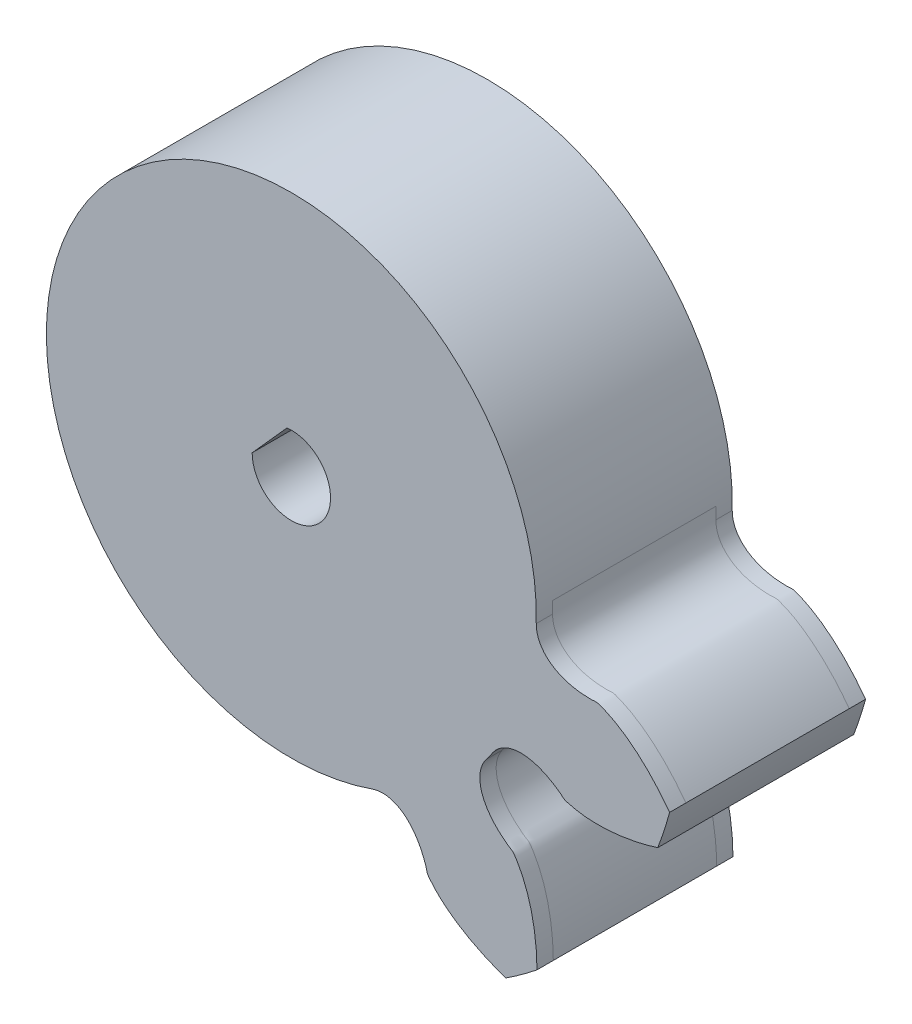
SolidWorks part; units mm, degrees
note: '?' marks a value the reader was unsure of.
ref_plane "Front Plane" through (0, 0, 0) normal (0, 0, 1) x (1, 0, 0)
ref_plane "Top Plane" through (0, 0, 0) normal (0, 1, 0) x (1, 0, 0)
ref_plane "Right Plane" through (0, 0, 0) normal (1, 0, 0) x (0, 0, -1)
ref_axis "Axis1" through (0, 0, 55) along (0, 0, -1)?
sketch "SketchRevolveSpur01" plane through (0, 0, 0) normal (1, 0, 0) x (0, 0, -1)
  line L0 (0, 0) -> (1, 0) construction
  line L1 (-3, 0) -> (-3, 12)
  line L2 (-3, 12) -> (3, 12)
  line L3 (3, 12) -> (3, 0)
  line L4 (3, 0) -> (-3, 0)
  dimension "Side1" = 3
  dimension "OutsideRadius" = 12
  dimension "Side2" = 3
revolve "Spur01" add sketch "SketchRevolveSpur01" angle 360 about L0
sketch "SketchToothSpur01" plane through (0, 0, 0) normal (0, 0, 1) x (1, 0, 0)
  arc A0 (11.6557, 3.249) -> (11.6557, -3.249) centre (0, 0) cw
  spline S0 degree 3 poles (11.6557, -3.249) (11.5423, -3.0893) (11.3677, -2.8624) (11.1235, -2.583) (10.948, -2.3979) (10.7762, -2.2308) (10.6093, -2.0811) (10.4483, -1.9481) (10.2945, -1.8312) (10.1487, -1.7294) (10.0119, -1.6419) (9.8851, -1.5678) (9.769, -1.5061) (9.6644, -1.4561) (9.5722, -1.4158) (9.4742, -1.38) (9.3515, -1.3286) (9.2141, -1.3558) (9.0897, -1.351) (8.9912, -1.3478) (8.8951, -1.3404) (8.8013, -1.3301) (8.7098, -1.3167) (8.6206, -1.3002) (8.5337, -1.2806) (8.4492, -1.2579) (8.3671, -1.232) (8.2873, -1.2028) (8.2098, -1.1702) (8.1347, -1.1342) (8.0621, -1.0944) (7.9919, -1.0508) (7.9244, -1.0029) (7.8597, -0.9507) (7.7981, -0.8936) (7.74, -0.8313) (7.686, -0.7636) (7.6368, -0.6902) (7.5934, -0.6111) (7.5566, -0.5264) (7.5278, -0.4366) (7.5078, -0.3426) (7.4995, -0.2566) (7.4964, -0.1421) (7.5027, 0) (7.4964, 0.1421) (7.4995, 0.2566) (7.5078, 0.3426) (7.5278, 0.4366) (7.5566, 0.5264) (7.5934, 0.6111) (7.6368, 0.6902) (7.686, 0.7636) (7.74, 0.8313) (7.7981, 0.8936) (7.8597, 0.9507) (7.9244, 1.0029) (7.9919, 1.0508) (8.0621, 1.0944) (8.1347, 1.1342) (8.2098, 1.1702) (8.2873, 1.2028) (8.3671, 1.232) (8.4492, 1.2579) (8.5337, 1.2806) (8.6206, 1.3002) (8.7098, 1.3167) (8.8013, 1.3301) (8.8951, 1.3404) (8.9912, 1.3478) (9.0897, 1.351) (9.2141, 1.3558) (9.3515, 1.3286) (9.4742, 1.38) (9.5722, 1.4158) (9.6644, 1.4561) (9.769, 1.5061) (9.8851, 1.5678) (10.0119, 1.6419) (10.1487, 1.7294) (10.2945, 1.8312) (10.4483, 1.9481) (10.6093, 2.0811) (10.7762, 2.2308) (10.948, 2.3979) (11.1235, 2.583) (11.3677, 2.8624) (11.5423, 3.0893) (11.6557, 3.249) knots 0 0 0 0 0.05171 0.075523 0.097976 0.119068 0.138799 0.15717 0.17418 0.189829 0.204117 0.217044 0.228611 0.238817 0.247662 0.255146 0.266488 0.281932 0.290791 0.299458 0.307939 0.316243 0.324379 0.332357 0.340187 0.347883 0.35546 0.362932 0.370318 0.37764 0.384918 0.392178 0.399448 0.406756 0.414133 0.42161 0.429217 0.436977 0.444912 0.453029 0.461324 0.469778 0.478358 0.484106 0.5 0.515894 0.521642 0.530222 0.538676 0.546971 0.555088 0.563023 0.570783 0.57839 0.585867 0.593244 0.600552 0.607822 0.615082 0.62236 0.629682 0.637068 0.64454 0.652117 0.659813 0.667643 0.675621 0.683757 0.692061 0.700542 0.709209 0.718068 0.733512 0.744854 0.752338 0.761183 0.771389 0.782956 0.795883 0.810171 0.82582 0.84283 0.861201 0.880932 0.902024 0.924477 0.94829 1 1 1 1
extrude "ToothExtrudeCutSpur01" cut sketch "SketchToothSpur01" against normal blind 2.5 and the other way blind 2.5
pattern_circular "PatternSpur01" count 3 every 36 about axis through (0, 0, 55) along (0, 0, -1) of "ToothExtrudeCutSpur01"
sketch "Sketch5" plane through (0, 0, 3) normal (0, 0, 1) x (1, 0, 0)
  circle A0 centre (0, 0) radius 7.5
  circle A1 centre (0, 0) radius 12
  spline S0 degree 3 poles (330.6086, 1970.8831) (-63.5307, -131.6267) (27.9115, -21.7923) (11.1235, -2.583) (10.948, -2.3979) (10.7762, -2.2308) (10.6093, -2.0811) (10.4483, -1.9481) (10.2945, -1.8312) (10.1487, -1.7294) (10.0119, -1.6419) (9.8851, -1.5678) (9.769, -1.5061) (9.6644, -1.4561) (9.5722, -1.4158) (9.4742, -1.38) (9.3515, -1.3286) (9.2141, -1.3558) (9.0897, -1.351) (8.9912, -1.3478) (8.8951, -1.3404) (8.8013, -1.3301) (8.7098, -1.3167) (8.6206, -1.3002) (8.5337, -1.2806) (8.4492, -1.2579) (8.3671, -1.232) (8.2873, -1.2028) (8.2098, -1.1702) (8.1347, -1.1342) (8.0621, -1.0944) (7.9919, -1.0508) (7.9244, -1.0029) (7.8597, -0.9507) (7.7981, -0.8936) (7.74, -0.8313) (7.686, -0.7636) (7.6368, -0.6902) (7.5934, -0.6111) (7.5566, -0.5264) (7.5278, -0.4366) (7.5078, -0.3426) (7.4995, -0.2566) (7.4964, -0.1421) (7.5027, 0) (7.4964, 0.1421) (7.4995, 0.2566) (7.5078, 0.3426) (7.5278, 0.4366) (7.5566, 0.5264) (7.5934, 0.6111) (7.6368, 0.6902) (7.686, 0.7636) (7.74, 0.8313) (7.7981, 0.8936) (7.8597, 0.9507) (7.9244, 1.0029) (7.9919, 1.0508) (8.0621, 1.0944) (8.1347, 1.1342) (8.2098, 1.1702) (8.2873, 1.2028) (8.3671, 1.232) (8.4492, 1.2579) (8.5337, 1.2806) (8.6206, 1.3002) (8.7098, 1.3167) (8.8013, 1.3301) (8.8951, 1.3404) (8.9912, 1.3478) (9.0897, 1.351) (9.2141, 1.3558) (9.3515, 1.3286) (9.4742, 1.38) (9.5722, 1.4158) (9.6644, 1.4561) (9.769, 1.5061) (9.8851, 1.5678) (10.0119, 1.6419) (10.1487, 1.7294) (10.2945, 1.8312) (10.4483, 1.9481) (10.6093, 2.0811) (10.7762, 2.2308) (10.948, 2.3979) (11.1235, 2.583) (27.9114, 21.7922) (-63.5294, 131.6251) (330.5997, -1970.8358) knots -6.637455 -6.637455 -6.637455 -6.637455 0.05171 0.075523 0.097976 0.119068 0.138799 0.15717 0.17418 0.189829 0.204117 0.217044 0.228611 0.238817 0.247662 0.255146 0.266488 0.281932 0.290791 0.299458 0.307939 0.316243 0.324379 0.332357 0.340187 0.347883 0.35546 0.362932 0.370318 0.37764 0.384918 0.392178 0.399448 0.406756 0.414133 0.42161 0.429217 0.436977 0.444912 0.453029 0.461324 0.469778 0.478358 0.484106 0.5 0.515894 0.521642 0.530222 0.538676 0.546971 0.555088 0.563023 0.570783 0.57839 0.585867 0.593244 0.600552 0.607822 0.615082 0.62236 0.629682 0.637068 0.64454 0.652117 0.659813 0.667643 0.675621 0.683757 0.692061 0.700542 0.709209 0.718068 0.733512 0.744854 0.752338 0.761183 0.771389 0.782956 0.795883 0.810171 0.82582 0.84283 0.861201 0.880932 0.902024 0.924477 0.94829 7.637405 7.637405 7.637405 7.637405 only from (11.5805, -3.145) to (11.5805, 3.145) construction
  spline S1 degree 3 poles (1425.924, 1400.1511) (-128.7657, -69.1458) (9.7717, -34.0363) (7.4809, -8.6279) (7.4477, -8.375) (7.4069, -8.1388) (7.3598, -7.9196) (7.3078, -7.7175) (7.2521, -7.5324) (7.194, -7.3643) (7.1347, -7.2132) (7.0756, -7.0787) (7.018, -6.9605) (6.9628, -6.8586) (6.9119, -6.7718) (6.8537, -6.6852) (6.7845, -6.5716) (6.6575, -6.5128) (6.5596, -6.4358) (6.4818, -6.3753) (6.4084, -6.3128) (6.3385, -6.2494) (6.2724, -6.1847) (6.2099, -6.119) (6.1512, -6.052) (6.0962, -5.984) (6.045, -5.9147) (5.9976, -5.8442) (5.954, -5.7723) (5.9145, -5.699) (5.8791, -5.6242) (5.848, -5.5476) (5.8214, -5.4692) (5.7998, -5.3889) (5.7836, -5.3065) (5.7732, -5.222) (5.7693, -5.1355) (5.7726, -5.0472) (5.784, -4.9577) (5.804, -4.8675) (5.8335, -4.7779) (5.8726, -4.6901) (5.9164, -4.6157) (5.9811, -4.5212) (6.0698, -4.41) (6.1482, -4.2913) (6.218, -4.2005) (6.2753, -4.1359) (6.3468, -4.0715) (6.4228, -4.0158) (6.5024, -3.9689) (6.584, -3.9304) (6.667, -3.9) (6.7504, -3.8769) (6.834, -3.8607) (6.9174, -3.8507) (7.0005, -3.8464) (7.0832, -3.8474) (7.1656, -3.8534) (7.2478, -3.8639) (7.3297, -3.8789) (7.4115, -3.8981) (7.4932, -3.9214) (7.5749, -3.9487) (7.6567, -3.98) (7.7384, -4.0151) (7.8203, -4.0542) (7.9022, -4.0971) (7.9841, -4.144) (8.0662, -4.1945) (8.1478, -4.2498) (8.2513, -4.319) (8.3465, -4.4218) (8.4759, -4.4524) (8.5762, -4.481) (8.6746, -4.5026) (8.7886, -4.5236) (8.9187, -4.5419) (9.0649, -4.5565) (9.2269, -4.5662) (9.4047, -4.5695) (9.598, -4.5653) (9.8063, -4.5523) (10.0293, -4.5294) (10.2665, -4.4952) (10.5174, -4.4486) (35.3899, 1.2244) (25.971, 143.8286) (-890.9674, -1788.7613) knots -6.637455 -6.637455 -6.637455 -6.637455 0.05171 0.075523 0.097976 0.119068 0.138799 0.15717 0.17418 0.189829 0.204117 0.217044 0.228611 0.238817 0.247662 0.255146 0.266488 0.281932 0.290791 0.299458 0.307939 0.316243 0.324379 0.332357 0.340187 0.347883 0.35546 0.362932 0.370318 0.37764 0.384918 0.392178 0.399448 0.406756 0.414133 0.42161 0.429217 0.436977 0.444912 0.453029 0.461324 0.469778 0.478358 0.484106 0.5 0.515894 0.521642 0.530222 0.538676 0.546971 0.555088 0.563023 0.570783 0.57839 0.585867 0.593244 0.600552 0.607822 0.615082 0.62236 0.629682 0.637068 0.64454 0.652117 0.659813 0.667643 0.675621 0.683757 0.692061 0.700542 0.709209 0.718068 0.733512 0.744854 0.752338 0.761183 0.771389 0.782956 0.795883 0.810171 0.82582 0.84283 0.861201 0.880932 0.902024 0.924477 0.94829 7.637405 7.637405 7.637405 7.637405 only from (7.5202, -9.3513) to (11.2175, -4.2625) construction
  spline S2 degree 3 poles (1976.5849, 294.6089) (-144.8165, 19.7464) (-12.1006, -33.2796) (0.9808, -11.3773) (1.1026, -11.1531) (1.2084, -10.9381) (1.2992, -10.7331) (1.3759, -10.539) (1.4396, -10.3565) (1.4914, -10.1864) (1.5323, -10.0293) (1.5636, -9.8857) (1.5864, -9.7563) (1.6016, -9.6414) (1.6115, -9.5412) (1.6152, -9.437) (1.6262, -9.3044) (1.5579, -9.1821) (1.524, -9.0623) (1.4966, -8.9676) (1.4739, -8.8739) (1.4547, -8.7815) (1.4392, -8.6904) (1.4273, -8.6004) (1.4191, -8.5118) (1.4146, -8.4244) (1.4139, -8.3383) (1.417, -8.2533) (1.424, -8.1696) (1.4351, -8.0871) (1.4505, -8.0057) (1.4703, -7.9255) (1.4949, -7.8465) (1.5247, -7.7688) (1.5599, -7.6925) (1.6012, -7.6181) (1.6489, -7.5458) (1.7035, -7.4764) (1.7653, -7.4106) (1.8345, -7.3494) (1.911, -7.2943) (1.9942, -7.2462) (2.0735, -7.2117) (2.1813, -7.1734) (2.3185, -7.1355) (2.4517, -7.0855) (2.5615, -7.0532) (2.6459, -7.0345) (2.7414, -7.0245) (2.8357, -7.0241) (2.9277, -7.0329) (3.0164, -7.0498) (3.1013, -7.0739) (3.1824, -7.1043) (3.2596, -7.1403) (3.3329, -7.1812) (3.4026, -7.2266) (3.469, -7.2761) (3.5322, -7.3293) (3.5924, -7.3861) (3.6499, -7.4464) (3.7048, -7.51) (3.7572, -7.5769) (3.8073, -7.647) (3.855, -7.7203) (3.9005, -7.7969) (3.9437, -7.8766) (3.9848, -7.9595) (4.0235, -8.0455) (4.0602, -8.1346) (4.0937, -8.2273) (4.1368, -8.3442) (4.1534, -8.4832) (4.2401, -8.5841) (4.3044, -8.6662) (4.3713, -8.7415) (4.4512, -8.8254) (4.5457, -8.9168) (4.6554, -9.0145) (4.7808, -9.1176) (4.9227, -9.2248) (5.0815, -9.335) (5.2577, -9.4469) (5.4516, -9.5594) (5.6636, -9.6712) (5.894, -9.7809) (29.3507, -19.8111) (105.5512, 101.0944) (-1772.2153, -923.4408) knots -6.637455 -6.637455 -6.637455 -6.637455 0.05171 0.075523 0.097976 0.119068 0.138799 0.15717 0.17418 0.189829 0.204117 0.217044 0.228611 0.238817 0.247662 0.255146 0.266488 0.281932 0.290791 0.299458 0.307939 0.316243 0.324379 0.332357 0.340187 0.347883 0.35546 0.362932 0.370318 0.37764 0.384918 0.392178 0.399448 0.406756 0.414133 0.42161 0.429217 0.436977 0.444912 0.453029 0.461324 0.469778 0.478358 0.484106 0.5 0.515894 0.521642 0.530222 0.538676 0.546971 0.555088 0.563023 0.570783 0.57839 0.585867 0.593244 0.600552 0.607822 0.615082 0.62236 0.629682 0.637068 0.64454 0.652117 0.659813 0.667643 0.675621 0.683757 0.692061 0.700542 0.709209 0.718068 0.733512 0.744854 0.752338 0.761183 0.771389 0.782956 0.795883 0.810171 0.82582 0.84283 0.861201 0.880932 0.902024 0.924477 0.94829 7.637405 7.637405 7.637405 7.637405 only from (0.5875, -11.9856) to (6.5697, -10.0419) construction
  spline S3 degree 3 poles (11.5805, -3.145) (11.4898, -3.0217) (11.3396, -2.8302) (11.1235, -2.583) (10.948, -2.3979) (10.7762, -2.2308) (10.6093, -2.0811) (10.4483, -1.9481) (10.2945, -1.8312) (10.1487, -1.7294) (10.0119, -1.6419) (9.8851, -1.5678) (9.769, -1.5061) (9.6644, -1.4561) (9.5722, -1.4158) (9.4742, -1.38) (9.3515, -1.3286) (9.2141, -1.3558) (9.0897, -1.351) (8.9912, -1.3478) (8.8951, -1.3404) (8.8013, -1.3301) (8.7098, -1.3167) (8.6206, -1.3002) (8.5337, -1.2806) (8.4492, -1.2579) (8.3671, -1.232) (8.2873, -1.2028) (8.2098, -1.1702) (8.1347, -1.1342) (8.0621, -1.0944) (7.9919, -1.0508) (7.9244, -1.0029) (7.8597, -0.9507) (7.7981, -0.8936) (7.74, -0.8313) (7.686, -0.7636) (7.6368, -0.6902) (7.5934, -0.6111) (7.5566, -0.5264) (7.5278, -0.4366) (7.5078, -0.3426) (7.4995, -0.2566) (7.4964, -0.1421) (7.5027, 0) (7.4964, 0.1421) (7.4995, 0.2566) (7.5078, 0.3426) (7.5278, 0.4366) (7.5566, 0.5264) (7.5934, 0.6111) (7.6368, 0.6902) (7.686, 0.7636) (7.74, 0.8313) (7.7981, 0.8936) (7.8597, 0.9507) (7.9244, 1.0029) (7.9919, 1.0508) (8.0621, 1.0944) (8.1347, 1.1342) (8.2098, 1.1702) (8.2873, 1.2028) (8.3671, 1.232) (8.4492, 1.2579) (8.5337, 1.2806) (8.6206, 1.3002) (8.7098, 1.3167) (8.8013, 1.3301) (8.8951, 1.3404) (8.9912, 1.3478) (9.0897, 1.351) (9.2141, 1.3558) (9.3515, 1.3286) (9.4742, 1.38) (9.5722, 1.4158) (9.6644, 1.4561) (9.769, 1.5061) (9.8851, 1.5678) (10.0119, 1.6419) (10.1487, 1.7294) (10.2945, 1.8312) (10.4483, 1.9481) (10.6093, 2.0811) (10.7762, 2.2308) (10.948, 2.3979) (11.1235, 2.583) (11.3396, 2.8302) (11.4898, 3.0217) (11.5805, 3.145) knots 0.011288 0.011288 0.011288 0.011288 0.05171 0.075523 0.097976 0.119068 0.138799 0.15717 0.17418 0.189829 0.204117 0.217044 0.228611 0.238817 0.247662 0.255146 0.266488 0.281932 0.290791 0.299458 0.307939 0.316243 0.324379 0.332357 0.340187 0.347883 0.35546 0.362932 0.370318 0.37764 0.384918 0.392178 0.399448 0.406756 0.414133 0.42161 0.429217 0.436977 0.444912 0.453029 0.461324 0.469778 0.478358 0.484106 0.5 0.515894 0.521642 0.530222 0.538676 0.546971 0.555088 0.563023 0.570783 0.57839 0.585867 0.593244 0.600552 0.607822 0.615082 0.62236 0.629682 0.637068 0.64454 0.652117 0.659813 0.667643 0.675621 0.683757 0.692061 0.700542 0.709209 0.718068 0.733512 0.744854 0.752338 0.761183 0.771389 0.782956 0.795883 0.810171 0.82582 0.84283 0.861201 0.880932 0.902024 0.924477 0.94829 0.988712 0.988712 0.988712 0.988712
  spline S4 degree 3 poles (7.5202, -9.3513) (7.5193, -9.1982) (7.5104, -8.955) (7.4809, -8.6279) (7.4477, -8.375) (7.4069, -8.1388) (7.3598, -7.9196) (7.3078, -7.7175) (7.2521, -7.5324) (7.194, -7.3643) (7.1347, -7.2132) (7.0756, -7.0787) (7.018, -6.9605) (6.9628, -6.8586) (6.9119, -6.7718) (6.8537, -6.6852) (6.7845, -6.5716) (6.6575, -6.5128) (6.5596, -6.4358) (6.4818, -6.3753) (6.4084, -6.3128) (6.3385, -6.2494) (6.2724, -6.1847) (6.2099, -6.119) (6.1512, -6.052) (6.0962, -5.984) (6.045, -5.9147) (5.9976, -5.8442) (5.954, -5.7723) (5.9145, -5.699) (5.8791, -5.6242) (5.848, -5.5476) (5.8214, -5.4692) (5.7998, -5.3889) (5.7836, -5.3065) (5.7732, -5.222) (5.7693, -5.1355) (5.7726, -5.0472) (5.784, -4.9577) (5.804, -4.8675) (5.8335, -4.7779) (5.8726, -4.6901) (5.9164, -4.6157) (5.9811, -4.5212) (6.0698, -4.41) (6.1482, -4.2913) (6.218, -4.2005) (6.2753, -4.1359) (6.3468, -4.0715) (6.4228, -4.0158) (6.5024, -3.9689) (6.584, -3.9304) (6.667, -3.9) (6.7504, -3.8769) (6.834, -3.8607) (6.9174, -3.8507) (7.0005, -3.8464) (7.0832, -3.8474) (7.1656, -3.8534) (7.2478, -3.8639) (7.3297, -3.8789) (7.4115, -3.8981) (7.4932, -3.9214) (7.5749, -3.9487) (7.6567, -3.98) (7.7384, -4.0151) (7.8203, -4.0542) (7.9022, -4.0971) (7.9841, -4.144) (8.0662, -4.1945) (8.1478, -4.2498) (8.2513, -4.319) (8.3465, -4.4218) (8.4759, -4.4524) (8.5762, -4.481) (8.6746, -4.5026) (8.7886, -4.5236) (8.9187, -4.5419) (9.0649, -4.5565) (9.2269, -4.5662) (9.4047, -4.5695) (9.598, -4.5653) (9.8063, -4.5523) (10.0293, -4.5294) (10.2665, -4.4952) (10.5174, -4.4486) (10.8375, -4.3755) (11.0716, -4.3089) (11.2175, -4.2625) knots 0.011288 0.011288 0.011288 0.011288 0.05171 0.075523 0.097976 0.119068 0.138799 0.15717 0.17418 0.189829 0.204117 0.217044 0.228611 0.238817 0.247662 0.255146 0.266488 0.281932 0.290791 0.299458 0.307939 0.316243 0.324379 0.332357 0.340187 0.347883 0.35546 0.362932 0.370318 0.37764 0.384918 0.392178 0.399448 0.406756 0.414133 0.42161 0.429217 0.436977 0.444912 0.453029 0.461324 0.469778 0.478358 0.484106 0.5 0.515894 0.521642 0.530222 0.538676 0.546971 0.555088 0.563023 0.570783 0.57839 0.585867 0.593244 0.600552 0.607822 0.615082 0.62236 0.629682 0.637068 0.64454 0.652117 0.659813 0.667643 0.675621 0.683757 0.692061 0.700542 0.709209 0.718068 0.733512 0.744854 0.752338 0.761183 0.771389 0.782956 0.795883 0.810171 0.82582 0.84283 0.861201 0.880932 0.902024 0.924477 0.94829 0.988712 0.988712 0.988712 0.988712
  spline S5 degree 3 poles (0.5875, -11.9856) (0.6767, -11.8612) (0.8124, -11.6592) (0.9808, -11.3773) (1.1026, -11.1531) (1.2084, -10.9381) (1.2992, -10.7331) (1.3759, -10.539) (1.4396, -10.3565) (1.4914, -10.1864) (1.5323, -10.0293) (1.5636, -9.8857) (1.5864, -9.7563) (1.6016, -9.6414) (1.6115, -9.5412) (1.6152, -9.437) (1.6262, -9.3044) (1.5579, -9.1821) (1.524, -9.0623) (1.4966, -8.9676) (1.4739, -8.8739) (1.4547, -8.7815) (1.4392, -8.6904) (1.4273, -8.6004) (1.4191, -8.5118) (1.4146, -8.4244) (1.4139, -8.3383) (1.417, -8.2533) (1.424, -8.1696) (1.4351, -8.0871) (1.4505, -8.0057) (1.4703, -7.9255) (1.4949, -7.8465) (1.5247, -7.7688) (1.5599, -7.6925) (1.6012, -7.6181) (1.6489, -7.5458) (1.7035, -7.4764) (1.7653, -7.4106) (1.8345, -7.3494) (1.911, -7.2943) (1.9942, -7.2462) (2.0735, -7.2117) (2.1813, -7.1734) (2.3185, -7.1355) (2.4517, -7.0855) (2.5615, -7.0532) (2.6459, -7.0345) (2.7414, -7.0245) (2.8357, -7.0241) (2.9277, -7.0329) (3.0164, -7.0498) (3.1013, -7.0739) (3.1824, -7.1043) (3.2596, -7.1403) (3.3329, -7.1812) (3.4026, -7.2266) (3.469, -7.2761) (3.5322, -7.3293) (3.5924, -7.3861) (3.6499, -7.4464) (3.7048, -7.51) (3.7572, -7.5769) (3.8073, -7.647) (3.855, -7.7203) (3.9005, -7.7969) (3.9437, -7.8766) (3.9848, -7.9595) (4.0235, -8.0455) (4.0602, -8.1346) (4.0937, -8.2273) (4.1368, -8.3442) (4.1534, -8.4832) (4.2401, -8.5841) (4.3044, -8.6662) (4.3713, -8.7415) (4.4512, -8.8254) (4.5457, -8.9168) (4.6554, -9.0145) (4.7808, -9.1176) (4.9227, -9.2248) (5.0815, -9.335) (5.2577, -9.4469) (5.4516, -9.5594) (5.6636, -9.6712) (5.894, -9.7809) (6.1959, -9.91) (6.4244, -9.9937) (6.5697, -10.0419) knots 0.011288 0.011288 0.011288 0.011288 0.05171 0.075523 0.097976 0.119068 0.138799 0.15717 0.17418 0.189829 0.204117 0.217044 0.228611 0.238817 0.247662 0.255146 0.266488 0.281932 0.290791 0.299458 0.307939 0.316243 0.324379 0.332357 0.340187 0.347883 0.35546 0.362932 0.370318 0.37764 0.384918 0.392178 0.399448 0.406756 0.414133 0.42161 0.429217 0.436977 0.444912 0.453029 0.461324 0.469778 0.478358 0.484106 0.5 0.515894 0.521642 0.530222 0.538676 0.546971 0.555088 0.563023 0.570783 0.57839 0.585867 0.593244 0.600552 0.607822 0.615082 0.62236 0.629682 0.637068 0.64454 0.652117 0.659813 0.667643 0.675621 0.683757 0.692061 0.700542 0.709209 0.718068 0.733512 0.744854 0.752338 0.761183 0.771389 0.782956 0.795883 0.810171 0.82582 0.84283 0.861201 0.880932 0.902024 0.924477 0.94829 0.988712 0.988712 0.988712 0.988712
  circle M8 centre (0, 0) radius 12
  dimension "D1" = 24
  dimension "D2" = 15
extrude "Cut-Extrude4" cut sketch "Sketch5" against normal through all contours S5 A0 S3 M8 | S4 A1 A0 | S5 A1 A0 | S3 A1 A0
sketch "AuxiliarySketchSpur01" plane through (0, 0, 0) normal (0, 0, 1) x (1, 0, 0)
  circle A0 centre (0, 0) radius 12.5 construction
  circle A1 centre (0, 0) radius 11.7462 construction
  circle A2 centre (0, 0) radius 12.2336 construction
  circle A3 centre (0, 0) radius 15 construction
  circle A4 centre (0, 0) radius 9 construction
  dimension "PitchDiameter" = 25
  dimension "BaseDiameter" = 23.4923
  dimension "FormDiameter" = 24.4671
  dimension "MajorDiameter" = 30
  dimension "MinorDiameter" = 18
scale "Scale1" bodies to scale 109 scale about origin uniform scaling yes scale factor 1.25
sketch "Sketch9" plane through (0, 0, -3.75) normal (0, 0, -1) x (-1, 0, 0)
  line L0 (1.5, 0) -> (0.1667, 1.4907)
  line L1 (0, 0) -> (0.8333, 0.7454) construction
  circle A0 centre (0, 0) radius 1.5
  dimension "D1" = 2
  dimension "D2" = 3
extrude "Cut-Extrude6" cut sketch "Sketch9" against normal through all
sketch "Sketch12" plane through (0, 0, -3.75) normal (0, 0, -1) x (-1, 0, 0)
  line L0 (1.5, 0) -> (0.1667, 1.4907) construction
  line L1 (1.5, 0) -> (0.1667, 1.4907)
  line L2 (4.279, 1.393) -> (1.8598, 4.0977)
  arc A0 (0.1667, 1.4907) -> (1.5, 0) centre (0, 0) ccw construction
  arc A1 (0.1667, 1.4907) -> (1.5, 0) centre (0, 0) ccw
  arc A2 (1.8598, 4.0977) -> (4.279, 1.393) centre (0, 0) ccw
  dimension "D1" = 3
extrude "Boss-Extrude3" add sketch "Sketch12" along normal blind 3
sketch "Sketch13" plane through (-3.0694, 2.7454, 0) normal (-0.7454, 0.6667, 0) x (0, 0, 1)
  line L0 (-6.75, 1.8143) -> (-3.75, -1.8143) construction
  circle A0 centre (-5.25, 0) radius 1
  dimension "D1" = 2
extrude "Cut-Extrude7" cut sketch "Sketch13" against normal blind 3
sketch "Sketch31" plane through (0, 0, 49.9908) normal (0, 0, 1) x (1, 0, 0)
